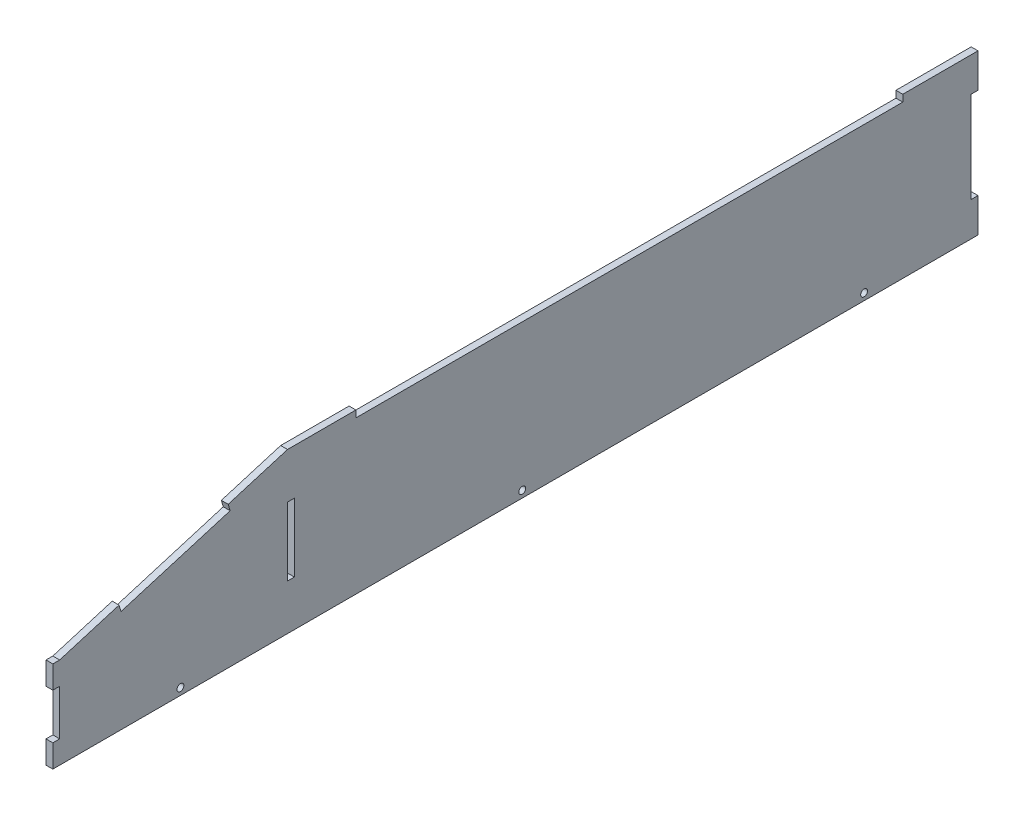
SolidWorks part; units mm, degrees
ref_plane "Front Plane" through (0, 0, 0) normal (0, 0, 1) x (1, 0, 0)
ref_plane "Top Plane" through (0, 0, 0) normal (0, 1, 0) x (1, 0, 0)
ref_plane "Right Plane" through (0, 0, 0) normal (1, 0, 0) x (0, 0, -1)
sketch "Sketch1" plane through (0, 0, 0) normal (1, 0, 0) x (0, 0, -1)
  line L0 (286.1443, 0.1739) -> (286.1443, 70.1739)
  line L1 (-16.8557, 70.1739) -> (286.1443, 70.1739)
  line L6 (-119.8557, 40.1739) -> (-116.8557, 40.1739)
  line L7 (-116.8557, 40.1739) -> (-16.8557, 70.1739)
  line L11 (-119.8557, 40.1739) -> (-119.8557, 0.1739)
  line L12 (-119.8557, 0.1739) -> (286.1443, 0.1739)
  dimension "D1" = 406
  dimension "D2" = 303
  dimension "D4" = 3
  dimension "D6" = 70
  dimension "D7" = 40
extrude "Boss-Extrude1" add sketch "Sketch1" along normal blind 3
sketch "Sketch5" plane through (3, 0, 0) normal (1, 0, 0) x (0, 0, -1)
  line L0 (286.1443, 55.1739) -> (283.1443, 55.1739)
  line L1 (286.1443, 0.1739) -> (286.1443, 70.1739) construction
  line L2 (283.1443, 55.1739) -> (283.1443, 15.1739)
  line L3 (283.1443, 15.1739) -> (286.1443, 15.1739)
  line L4 (-119.8557, 0.1739) -> (286.1443, 0.1739) construction
  dimension "D1" = 3
  dimension "D2" = 40
  dimension "D3" = 15
extrude "Cut-Extrude2" cut sketch "Sketch5" against normal blind 3 and the other way through all
sketch "Sketch6" plane through (3, 0, 0) normal (1, 0, 0) x (0, 0, -1)
  line L0 (253.1443, 70.1739) -> (253.1443, 67.1739)
  line L1 (286.1443, 70.1739) -> (-16.8557, 70.1739) construction
  line L2 (253.1443, 67.1739) -> (13.1443, 67.1739)
  line L3 (13.1443, 67.1739) -> (13.1443, 70.1739)
  line L4 (286.1443, 55.1739) -> (286.1443, 70.1739) construction
  dimension "D1" = 3
  dimension "D2" = 240
  dimension "D3" = 33
extrude "Cut-Extrude6" cut sketch "Sketch6" against normal blind 3 and the other way through all flip side to cut
sketch "Sketch7" plane through (3, 0, 0) normal (1, 0, 0) x (0, 0, -1)
  line L0 (-42.9086, 62.358) -> (-42.0465, 59.4846)
  line L1 (-16.8557, 70.1739) -> (-116.8557, 40.1739) construction
  line L2 (-42.0465, 59.4846) -> (-89.9378, 45.1172)
  line L3 (-89.9378, 45.1172) -> (-90.7999, 47.9906)
  dimension "D1" = 3
  dimension "D2" = 50
  dimension "D3" = 27.2
  dimension "D4" = 27.2031
extrude "Cut-Extrude11" cut sketch "Sketch7" against normal blind 3 and the other way through all flip side to cut
sketch "Sketch8" plane through (3, 0, 0) normal (1, 0, 0) x (0, 0, -1)
  line L0 (-119.8557, 30.1739) -> (-116.8557, 30.1739)
  line L1 (-119.8557, 40.1739) -> (-119.8557, 0.1739) construction
  line L2 (-116.8557, 30.1739) -> (-116.8557, 10.1739)
  line L3 (-116.8557, 10.1739) -> (-119.8557, 10.1739)
  line L4 (-119.8557, 0.1739) -> (286.1443, 0.1739) construction
  dimension "D1" = 3
  dimension "D2" = 20
  dimension "D3" = 10
extrude "Cut-Extrude12" cut sketch "Sketch8" against normal blind 3 and the other way through all flip side to cut
sketch "Sketch9" plane through (3, 0, 0) normal (1, 0, 0) x (0, 0, -1)
  line L0 (-16.8557, 50.1739) -> (-16.8557, 20.1739)
  line L1 (-16.8557, 20.1739) -> (-13.8557, 20.1739)
  line L2 (-13.8557, 20.1739) -> (-13.8557, 50.1739)
  line L3 (-13.8557, 50.1739) -> (-16.8557, 50.1739)
  line L4 (-119.8557, 0.1739) -> (286.1443, 0.1739) construction
  dimension "D1" = 30
  dimension "D2" = 20
  dimension "D3" = 3
extrude "Cut-Extrude13" cut sketch "Sketch9" against normal blind 3
sketch "Sketch10" plane through (3, 0, 0) normal (1, 0, 0) x (0, 0, -1)
  line L0 (-119.8557, 0.1739) -> (286.1443, 0.1739) construction
  line L1 (286.1443, 0.1739) -> (286.1443, 15.1739) construction
  circle A0 centre (236.1443, 3.1739) radius 1.5
  circle A1 centre (86.1443, 3.1739) radius 1.5
  circle A2 centre (-63.8557, 3.1739) radius 1.5
  dimension "D1" = 3
  dimension "D2" = 3
  dimension "D3" = 50
  dimension "D4" = 3
extrude "Cut-Extrude14" cut sketch "Sketch10" against normal blind 10
